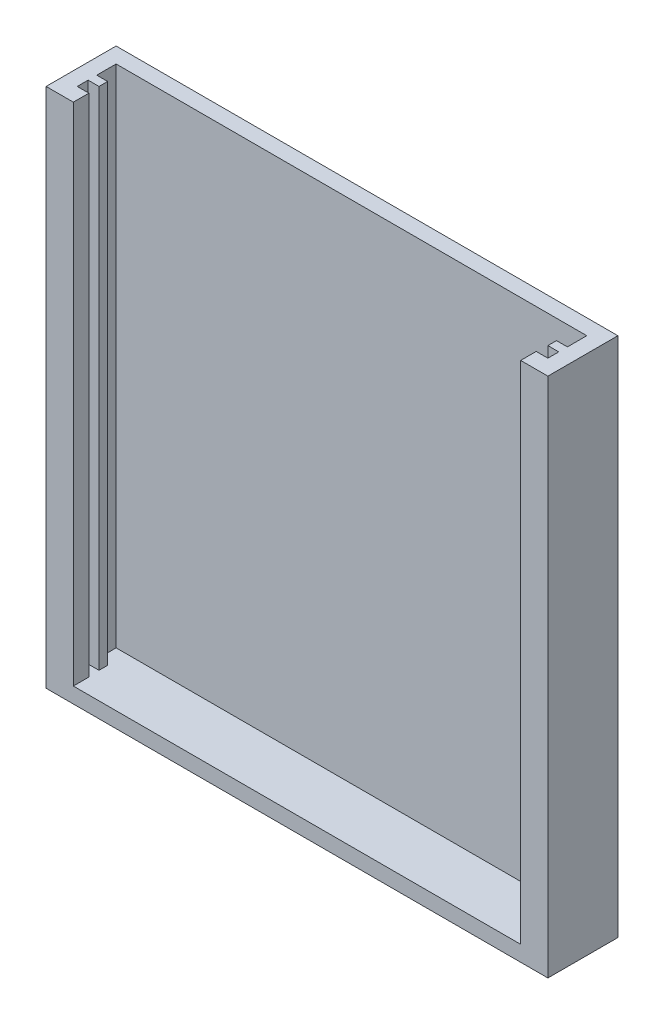
SolidWorks part; units mm, degrees
ref_plane "Front Plane" through (0, 0, 0) normal (0, 0, 1) x (1, 0, 0)
ref_plane "Top Plane" through (0, 0, 0) normal (0, 1, 0) x (1, 0, 0)
ref_plane "Right Plane" through (0, 0, 0) normal (1, 0, 0) x (0, 0, -1)
sketch "Sketch8" plane through (0, 0, 0) normal (0, 1, 0) x (1, 0, 0)
  line L0 (-2.6978, 0.4813) -> (56.8644, 0.4813)
  line L1 (56.8644, 0.4813) -> (56.8644, -2.0093)
  line L2 (56.8644, -2.0093) -> (55.4644, -2.0093)
  line L3 (55.4644, -2.0093) -> (55.4644, -3.1187)
  line L4 (55.4644, -3.1187) -> (56.8644, -3.1187)
  line L5 (56.8644, -3.1187) -> (56.8644, -4.5187)
  line L6 (56.8644, -4.5187) -> (55.3644, -4.5187)
  line L7 (55.3644, -4.5187) -> (55.3644, -6.5187)
  line L8 (55.3644, -6.5187) -> (58.8644, -6.5187)
  line L9 (58.8644, -6.5187) -> (58.8644, 2.4813)
  line L10 (58.8644, 2.4813) -> (-5.6356, 2.4813)
  line L11 (-5.6356, 2.4813) -> (-5.6356, -6.5187)
  line L12 (-5.6356, -6.5187) -> (-2.1356, -6.5187)
  line L13 (-2.1356, -6.5187) -> (-2.1356, -4.5187)
  line L14 (-2.1356, -4.5187) -> (-3.6356, -4.5187)
  line L15 (-3.6356, -4.5187) -> (-3.6356, -3.1187)
  line L16 (-3.6356, -3.1187) -> (-2.2356, -3.1187)
  line L17 (-2.2356, -3.1187) -> (-2.2356, -2.0093)
  line L18 (-2.2356, -2.0093) -> (-3.6356, -2.0093)
  line L19 (-3.6356, -2.0093) -> (-3.6356, 0.4813)
  line L20 (-3.6356, 0.4813) -> (-2.6978, 0.4813)
  point P2 (-3.6356, -3.8187)
  dimension "D1" = 1.4
  dimension "D2" = 1.4
  dimension "D3" = 1.5
  dimension "D4" = 1.5
  dimension "D5" = 1.4
  dimension "D6" = 1.4
  dimension "D7" = 2
  dimension "D8" = 2
  dimension "D9" = 2
  dimension "D10" = 2
  dimension "D11" = 2
  dimension "D12" = 2
  dimension "D13" = 2
  dimension "D14" = 9
  dimension "D15" = 9
  dimension "D16" = 64.5
extrude "Boss-Extrude1" add sketch "Sketch8" along normal blind 65
sketch "Sketch9" plane through (0, 0, 0) normal (0, -1, 0) x (1, 0, 0)
  line L1 (-5.6356, 6.5187) -> (58.8644, 6.5187)
  line L2 (-5.6356, 6.5187) -> (-5.6356, -2.4813)
  line L3 (-5.6356, -2.4813) -> (58.8644, -2.4813)
  line L4 (58.8644, 6.5187) -> (58.8644, -2.4813)
extrude "Boss-Extrude2" add sketch "Sketch9" along normal blind 2
